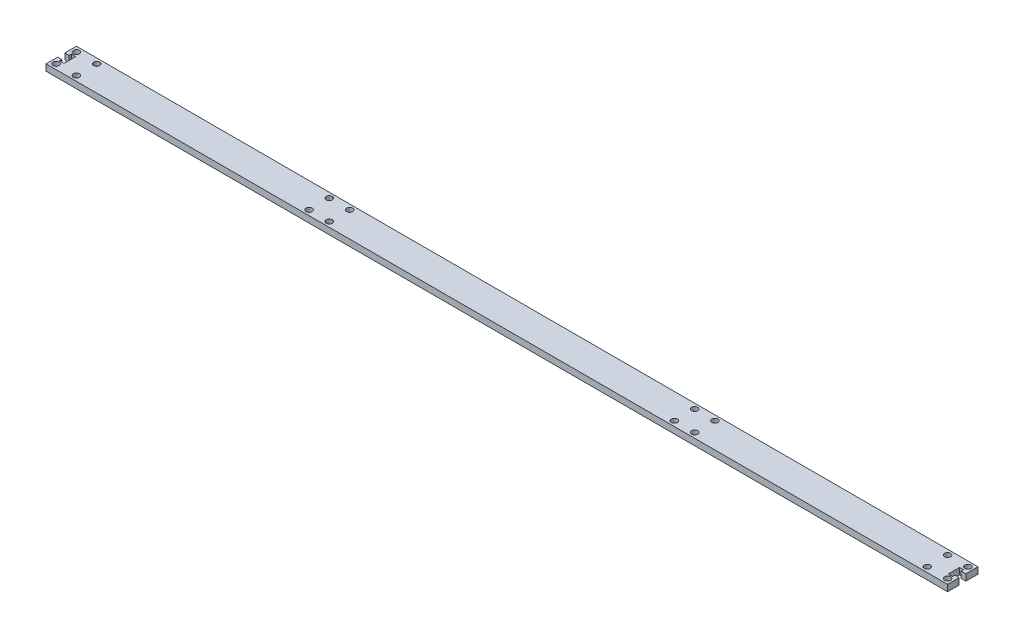
SolidWorks part; units mm, degrees
ref_plane "Front Plane" through (0, 0, 0) normal (0, 0, 1) x (1, 0, 0)
ref_plane "Top Plane" through (0, 0, 0) normal (0, 1, 0) x (1, 0, 0)
ref_plane "Right Plane" through (0, 0, 0) normal (1, 0, 0) x (0, 0, -1)
sketch "Sketch1" plane through (0, 0, 0) normal (0, 1, 0) x (1, 0, 0)
  line L0 (139.7, 7.5) -> (132.2, 7.5)
  line L1 (0, 0) -> (139.7, 0)
  line L2 (0, 0) -> (0, 15)
  line L3 (0, 15) -> (139.7, 15)
  line L4 (139.7, 0) -> (139.7, 15)
  line L5 (0, 7.5) -> (7.5, 7.5)
  line L6 (7.5, 7.5) -> (7.5, 12.5)
  line L7 (7.5, 12.5) -> (2.5, 12.5)
  line L8 (7.5, 12.5) -> (12.5, 12.5)
  line L9 (7.5, 7.5) -> (7.5, 2.5)
  line L10 (7.5, 2.5) -> (2.5, 2.5)
  line L11 (7.5, 2.5) -> (12.5, 2.5)
  line L12 (69.85, 0) -> (69.85, 15)
  line L13 (139.7, 0) -> (139.7, 15)
  line L14 (139.7, 0) -> (304.8, 0)
  line L15 (139.7, 15) -> (304.8, 15)
  line L16 (222.25, 0) -> (222.25, 15)
  line L17 (304.8, 0) -> (304.8, 15)
  line L18 (444.5, 15) -> (304.8, 15)
  line L19 (304.8, 0) -> (304.8, 15)
  line L20 (444.5, 0) -> (304.8, 0)
  line L21 (444.5, 0) -> (444.5, 15)
  circle A0 centre (2.5, 2.5) radius 1.5
  circle A1 centre (2.5, 12.5) radius 1.5
  circle A2 centre (12.5, 12.5) radius 1.5
  circle A3 centre (12.5, 2.5) radius 1.5
  circle A4 centre (137.2, 12.5) radius 1.5
  circle A5 centre (127.2, 12.5) radius 1.5
  circle A6 centre (137.2, 2.5) radius 1.5
  circle A7 centre (127.2, 2.5) radius 1.5
  circle A8 centre (432, 12.5) radius 1.5
  circle A9 centre (442, 12.5) radius 1.5
  circle A10 centre (442, 2.5) radius 1.5
  circle A11 centre (432, 2.5) radius 1.5
  circle A12 centre (307.3, 12.5) radius 1.5
  circle A13 centre (317.3, 12.5) radius 1.5
  circle A14 centre (317.3, 2.5) radius 1.5
  circle A15 centre (307.3, 2.5) radius 1.5
  dimension "D11" = 82.55
  dimension "D1" = 15
  dimension "D2" = 139.7
  dimension "D3" = 7.5
  dimension "D4" = 7.5
  dimension "D5" = 5
  dimension "D6" = 5
  dimension "D7" = 5
  dimension "D8" = 5
  dimension "D9" = 5
  dimension "D10" = 5
extrude "Boss-Extrude1" add sketch "Sketch1" along normal blind 3.175 contours A3 A0 L2 L1 L12 L3 A1 A2 | L12 L1 L4 L3 A6 A4 A5 A7 | L14 L16 L15 L4 | L14 L17 L15 L16 | L20 L21 L18 L17 A15 A14 A13 A12 A10 A8 A9 A11 region at (35.6856, 0, -7.5) region at (104.0144, 0, -7.5) region at (180.975, 0, -7.5) region at (263.525, 0, -7.5) region at (374.65, 0, -7.5)
sketch "Sketch4" plane through (0, 3.175, 0) normal (0, 1, 0) x (1, 0, 0)
  line L0 (444.5, 7.5) -> (432.4339, 7.5)
  line L1 (444.5, 0) -> (444.5, 15) construction
  line L2 (0, 15) -> (444.5, 15) construction
  line L3 (222.25, 15) -> (222.25, 0)
  line L4 (0, 0) -> (444.5, 0) construction
  line L5 (444.5, 9) -> (442.2, 9)
  line L6 (442.2, 9) -> (442.2, 10.15)
  line L7 (442.2, 10.15) -> (440.5, 10.15)
  line L8 (440.5, 10.15) -> (440.5, 7.5)
  line L9 (444.5, 9.25) -> (442.45, 9.25)
  line L10 (442.45, 9.25) -> (442.45, 10.4)
  line L11 (442.45, 10.4) -> (440.25, 10.4)
  line L12 (440.25, 10.4) -> (440.25, 7.5)
  line L13 (444.5, 5.75) -> (442.45, 5.75)
  line L14 (442.45, 5.75) -> (442.45, 4.6)
  line L15 (442.45, 4.6) -> (440.25, 4.6)
  line L16 (440.25, 4.6) -> (440.25, 7.5)
  line L17 (0, 9.25) -> (2.05, 9.25)
  line L18 (2.05, 9.25) -> (2.05, 10.4)
  line L19 (0, 5.75) -> (2.05, 5.75)
  line L20 (2.05, 5.75) -> (2.05, 4.6)
  line L21 (2.05, 4.6) -> (4.25, 4.6)
  line L22 (4.25, 4.6) -> (4.25, 7.5)
  line L23 (4.25, 10.4) -> (4.25, 7.5)
  line L24 (2.05, 10.4) -> (4.25, 10.4)
  line L25 (0, 9.25) -> (0, 5.75)
  line L26 (444.5, 9.25) -> (444.5, 5.75)
  line M20 (0, 15) -> (0, 0)
  line M22 (444.5, 0) -> (444.5, 15)
  dimension "D1" = 1.5
  dimension "D2" = 1.15
  dimension "D3" = 1.7
  dimension "D4" = 2.65
  dimension "D5" = 2.3
  dimension "D6" = 0.25
extrude "Cut-Extrude2" cut sketch "Sketch4" against normal blind 10 contours L16 L15 L14 L13 L0 M22 | L7 L8 L0 L5 L6 M22 | L24 L18 L17 L19 L20 L21 L22 L23 M20 region at (442.1148, 3.175, -6.257) region at (442.2174, 3.175, -8.5756) region at (2.3852, 3.175, -7.5)
sketch "Sketch6" plane through (440.5, 0, 0) normal (1, 0, 0) x (0, 0, -1)
  line L0 (10.15, 0) -> (7.5, 0) construction
  line L5 (7.5, 3.175) -> (10.15, 3.175)
  line L6 (7.5, 3.175) -> (7.5, 0)
  line L7 (7.5, 0) -> (10.15, 0)
  line L8 (10.15, 3.175) -> (10.15, 0)
extrude "Cut-Extrude3" cut sketch "Sketch6" against normal blind 0.25
